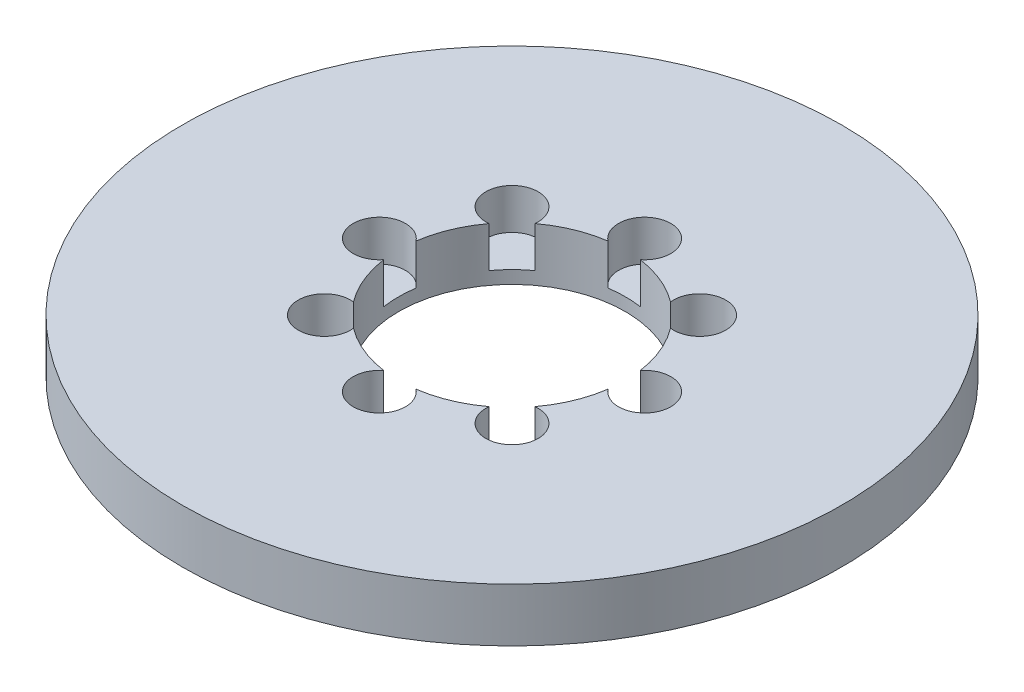
SolidWorks part; units mm, degrees
ref_plane "Front Plane" through (0, 0, 0) normal (0, 0, 1) x (1, 0, 0)
ref_plane "Top Plane" through (0, 0, 0) normal (0, 1, 0) x (1, 0, 0)
ref_plane "Right Plane" through (0, 0, 0) normal (1, 0, 0) x (0, 0, -1)
sketch "Sketch1" plane through (0, 0, 0) normal (0, 1, 0) x (1, 0, 0)
  circle A0 centre (0, 0) radius 80
  dimension "FLANGE_OD" = 160
extrude "Boss-Extrude1" add sketch "Sketch1" along normal blind 13
sketch "Sketch2" plane through (0, 0, 0) normal (0, 1, 0) x (1, 0, 0)
  circle A0 centre (0, 0) radius 27.5
  dimension "BORE_D" = 55
extrude "Cut-Extrude1" cut sketch "Sketch2" along normal through all
sketch "Sketch3" plane through (0, 13, 0) normal (0, 1, 0) x (1, 0, 0)
  circle A0 centre (0, 0) radius 32.2042 construction
  circle A1 centre (-32.2042, 0) radius 6.3449
  dimension "BOLT_D" = 12.6898
  dimension "BOLT_PCD" = 64.4083
extrude "Cut-Extrude2" cut sketch "Sketch3" against normal blind 9.8774
pattern_circular "CirPattern1" count 8 over 360 about axis through (0, 0, 0) along (0, 1, 0) of "Cut-Extrude2"
